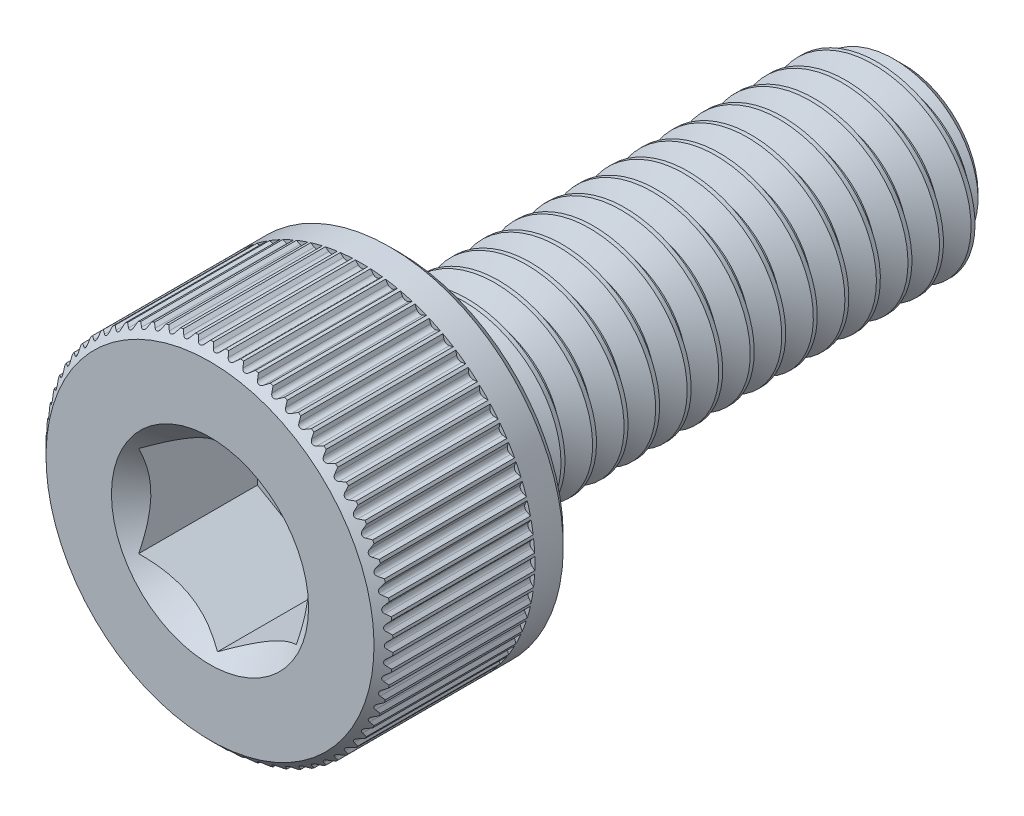
SolidWorks part; units mm, degrees
ref_plane "Front Plane" through (0, 0, 0) normal (0, 0, 1) x (1, 0, 0)
ref_plane "Top Plane" through (0, 0, 0) normal (0, 1, 0) x (1, 0, 0)
ref_plane "Right Plane" through (0, 0, 0) normal (1, 0, 0) x (0, 0, -1)
sketch "Sketch1" plane through (0, 0, 0) normal (1, 0, 0) x (0, 0, -1)
  line L0 (-5.5, 0) -> (5.5, 0) construction
  line L1 (5.5, 0) -> (5.5, 1.1752) construction
  line L2 (5.5, 1.1752) -> (5.1752, 1.5) construction
  line L3 (5.1752, 1.5) -> (5.125, 1.5) construction
  line L4 (5.125, 1.5) -> (-2.5, 1.5) construction
  line L5 (-2.5, 1.5) -> (-2.5, 2.75) construction
  line L6 (-2.5, 2.75) -> (-5.5, 2.75) construction
  line L7 (-5.5, 2.75) -> (-5.5, 0) construction
  line L8 (5.5, 1.1752) -> (5.5, 1.5) construction
  line L9 (5.4688, 1.5541) -> (5.7188, 1.1211) construction
  line L10 (5.7188, 1.1211) -> (5.9688, 1.5541) construction
  line L11 (5.9688, 1.5541) -> (5.4688, 1.5541) construction
  line L12 (5.7188, 1.5541) -> (5.7188, 1.5) construction
  line L13 (5.7188, 1.1211) -> (5.7188, 1.1752) construction
  line L14 (5.6875, 1.1752) -> (5.75, 1.1752) construction
  line L15 (5.5, 1.5) -> (5.9375, 1.5) construction
  line L16 (5.4844, 1.5271) -> (5.9531, 1.5271) construction
  line L17 (5.5, 0) -> (5.5, -1.5) construction
  line L18 (-2.65, 2.75) -> (-2.5, 2.6) construction
  line L19 (-5.35, 2.75) -> (-5.5, 2.6) construction
  line L20 (-2.5, 1.5) -> (-2.5, 0) construction
  line L21 (-2.5, 0.75) -> (0.1667, 0.75) construction
  line L22 (0.1667, 0.75) -> (2.8333, 0.75) construction
  line L23 (2.8333, 0.75) -> (5.5, 0.75) construction
  line L24 (0.1667, 0.75) -> (0.1667, 1.5) construction
  line L25 (0.1667, 1.5) -> (0.1667, 2.75) construction
  line L26 (2.8333, 0.75) -> (2.8333, 2.75) construction
  point P0 (-5.5, 1.25)
  point P3 (4.25, 1.5)
  point P4 (0, 0)
  point P18 (2.8333, 1.5)
  point P22 (5.7188, 1.1752)
  point P24 (5.125, 1.5)
  point P25 (5.7188, 1.5)
  point P28 (5.7188, 1.5271)
  point P29 (4.25, -1.5)
  point P30 (0.1667, 1.5)
  point P31 (-4, 2.75)
  point P37 (-3.025, 2.75)
  point P38 (-5.275, 2.75)
  point P45 (0.1667, 0.75)
  point P46 (2.8333, 0.75)
  dimension "D2" = 0.0625
  dimension "D7" = 0.15
  dimension "D8" = 0.15
  dimension "D9" = 0.15
  dimension "D10" = 0.075
  dimension "D11" = 0.375
  dimension "Drive Size" = 2.5
  dimension "Head Diameter" = 5.5
  dimension "Head Height" = 3
  dimension "Thread Pitch" = 0.5
  dimension "Thread Size" = 3
  dimension "Length" = 8
  dimension "D12" = 0.375
  dimension "D4" = 1.25
  dimension "D3" = 45
sketch "Sketch2" plane through (0, 0, 0) normal (1, 0, 0) x (0, 0, -1)
  line L0 (-5.5, 0) -> (-5.5, 2.6)
  line L1 (-5.35, 2.75) -> (-2.65, 2.75)
  line L2 (-2.5, 2.6) -> (-2.5, 1.65)
  line L4 (5.1752, 1.5) -> (5.5, 1.1752)
  line L5 (5.5, 1.1752) -> (5.5, 0)
  line L6 (-2.5, 2.75) -> (-5.5, 2.75) construction
  line L7 (5.5, 0) -> (-5.5, 0)
  line L8 (-5.35, 2.75) -> (-5.5, 2.6) construction
  line L10 (-5.35, 2.75) -> (-5.5, 2.6)
  line L14 (-2.65, 2.75) -> (-2.5, 2.6) construction
  line L16 (-2.65, 2.75) -> (-2.5, 2.6)
  line L17 (-2.5, 1.5) -> (-2.5, 2.75) construction
  line L19 (-2.35, 1.5) -> (5.1752, 1.5)
  line L20 (5.125, 1.5) -> (-2.5, 1.5) construction
  arc A1 (-2.5, 1.65) -> (-2.35, 1.5) centre (-2.35, 1.65) ccw
revolve "Revolve1" add sketch "Sketch2" angle 360 about L7
sketch "Sketch3" plane through (0, 0, 5.5) normal (0, 0, 1) x (1, 0, 0)
  line L1 (1.25, -0.7217) -> (1.25, 0.7217)
  line L2 (1.25, 0.7217) -> (0, 1.4434)
  line L3 (0, 1.4434) -> (-1.25, 0.7217)
  line L4 (-1.25, 0.7217) -> (-1.25, -0.7217)
  line L5 (-1.25, -0.7217) -> (0, -1.4434)
  line L6 (0, -1.4434) -> (1.25, -0.7217)
  circle A0 centre (0, 0) radius 1.25 construction
  circle A1 centre (0, 0) radius 2.75 construction
  circle A2 centre (0, 0) radius 2.75 construction
  circle A3 centre (0, 0) radius 1.4434 construction
  point P13 (0, 0)
extrude "Cut-Extrude1" cut sketch "Sketch3" against normal offset from surface (2 mm away) 1 up to face at (0, 2.6, 2.5)
sketch "Sketch4" plane through (0, 0, 5.5) normal (0, 0, 1) x (1, 0, 0)
  circle A0 centre (0, 0) radius 1.5625
  dimension "D1" = 3.125
extrude "Cut-Extrude2" cut sketch "Sketch4" against normal up to vertex (1.5 mm away) draft 45 up to point (0, 2.75, 4)
sketch "Sketch11" plane through (0, 0, 0) normal (1, 0, 0) x (0, 0, -1)
  line L0 (-5.5, 0) -> (5.5, 0) construction
  line L1 (-5.5, 0) -> (5.5, 0) construction
  line L2 (-1, 0) -> (-1, 1.5) construction
  line L3 (5.125, 1.5) -> (-2.5, 1.5) construction
  line L4 (4, 0) -> (4, 1.5) construction
  line L6 (5.5, 1.1752) -> (5.5, 1.5) construction
  point P2 (-1, 0)
  point P3 (4, 0)
  dimension "D1" = 1.5
  dimension "D2" = 1.5
sketch "Sketch6" plane through (0, 0, -5.5) normal (0, 0, -1) x (-1, 0, 0)
  circle A0 centre (0, 0) radius 1.5
curve "Helix/Spiral1" pitch 0.5 height 8.5 turns 17
sketch "Sketch10" plane through (0, 0, 0) normal (1, 0, 0) x (0, 0, -1)
  line L0 (-2.35, -2.75) -> (-2.35, 2.75)
  line L5 (-5.5, 0) -> (5.5, 0) construction
  line L6 (-2.35, 1.5) -> (-2.35, -1.5) construction
  point P3 (-2.35, 0)
split "Split1" trim tools "Sketch10" bodies to split 106 resulting bodies 114 115
sketch "Sketch7" plane through (0, 0, 0) normal (1, 0, 0) x (0, 0, -1)
  line L0 (5.4844, 1.5271) -> (5.9531, 1.5271)
  line L1 (5.9531, 1.5271) -> (5.75, 1.1752)
  line L2 (5.75, 1.1752) -> (5.6875, 1.1752)
  line L3 (5.6875, 1.1752) -> (5.4844, 1.5271)
sweep "Cut-Sweep1" cut profiles "Sketch7" path "Helix/Spiral1" align with end faces yes
sketch "Sketch8" plane through (0, 0, 0) normal (1, 0, 0) x (0, 0, -1)
  line L0 (-2.5, 0) -> (-2.5, 1.5)
  line L1 (-2.35, -1.5) -> (-2.35, 1.5) construction
  line L2 (-2.5, 1.5) -> (-2.35, 1.5)
  line L4 (-2.35, 1.5) -> (-1.484, 0)
  line L5 (-1.484, 0) -> (-2.5, 0)
  line L6 (5.125, 1.5) -> (-2.5, 1.5) construction
  line L7 (-5.5, 0) -> (5.5, 0) construction
  dimension "D1" = 60
revolve "Revolve2" add sketch "Sketch8" angle 360 about L5
ref_plane "Plane1" through (0, 0, 5.5) normal (0, 0, 1) x (1, 0, 0)
sketch "Sketch12" plane through (0, 0, 5.5) normal (0, 0, 1) x (1, 0, 0)
  line L0 (0, 0) -> (0.096, 2.7483) construction
  line L1 (0, 0) -> (-0.096, 2.7483) construction
  line L2 (0, 2.6812) -> (0, 2.8187) construction
  line L3 (-0.1664, 2.8187) -> (0.1664, 2.8187)
  line L4 (-0.1664, 2.8187) -> (-0.0493, 2.7017)
  line L5 (0.0493, 2.7017) -> (0.1664, 2.8187)
  circle A0 centre (0, 0) radius 2.75 construction
  arc A1 (-0.0493, 2.7017) -> (0.0493, 2.7017) centre (0, 2.751) ccw
  point P9 (0, 2.8187)
  point P13 (0, 2.75)
  dimension "D1" = 4
  dimension "D2" = 0.0688
extrude "Cut-Extrude3" cut sketch "Sketch12" against normal blind 2.4
pattern_circular "CirPattern1" count 72 over 360 about axis through (0, 0, 0) along (0, 0, 1) of "Cut-Extrude3"
equation "\"D2@Sketch1\" = \"Thread Pitch@Sketch1\" / 8"
equation "\"D4@Helix/Spiral1\" = \"Thread Pitch@Sketch1\""
equation "\"D7@Sketch1\" = \"Head Height@Sketch1\" * .05"
equation "\"D8@Sketch1\"=\"D7@Sketch1\""
equation "\"D9@Sketch1\"=\"D7@Sketch1\""
equation "\"D10@Sketch1\"=\"D7@Sketch1\"/2"
equation "\"D11@Sketch1\"=\"D10@Sketch1\"*5"
equation "\"D4@Sketch1\"=\"Thread Pitch@Sketch1\"*2.5"
equation "\"D12@Sketch1\"=\"Thread Pitch@Sketch1\"*.75"
equation "\"D3@Helix/Spiral1\"=\"Length@Sketch1\"+\"Thread Pitch@Sketch1\""
equation "\"D3@Sketch2\" = \"Thread Size@Sketch1\" * 0.05"
equation "\"D1@Sketch11\"=\"Length@Sketch1\"*0.1875"
equation "\"D2@Sketch11\"=\"D1@Sketch11\""
equation "\"D2@Sketch12\"=\"Head Diameter@Sketch1\"*.0125"
equation "\"D1@Cut-Extrude3\"=\"Head Height@Sketch1\"*.8"
equation "\"D1@CirPattern1\"=\"D3@CirPattern1\"/(1.25*\"D1@Sketch12\")"
equation "\"D1@Sketch4\"=\"Drive Size@Sketch1\"*1.25"
